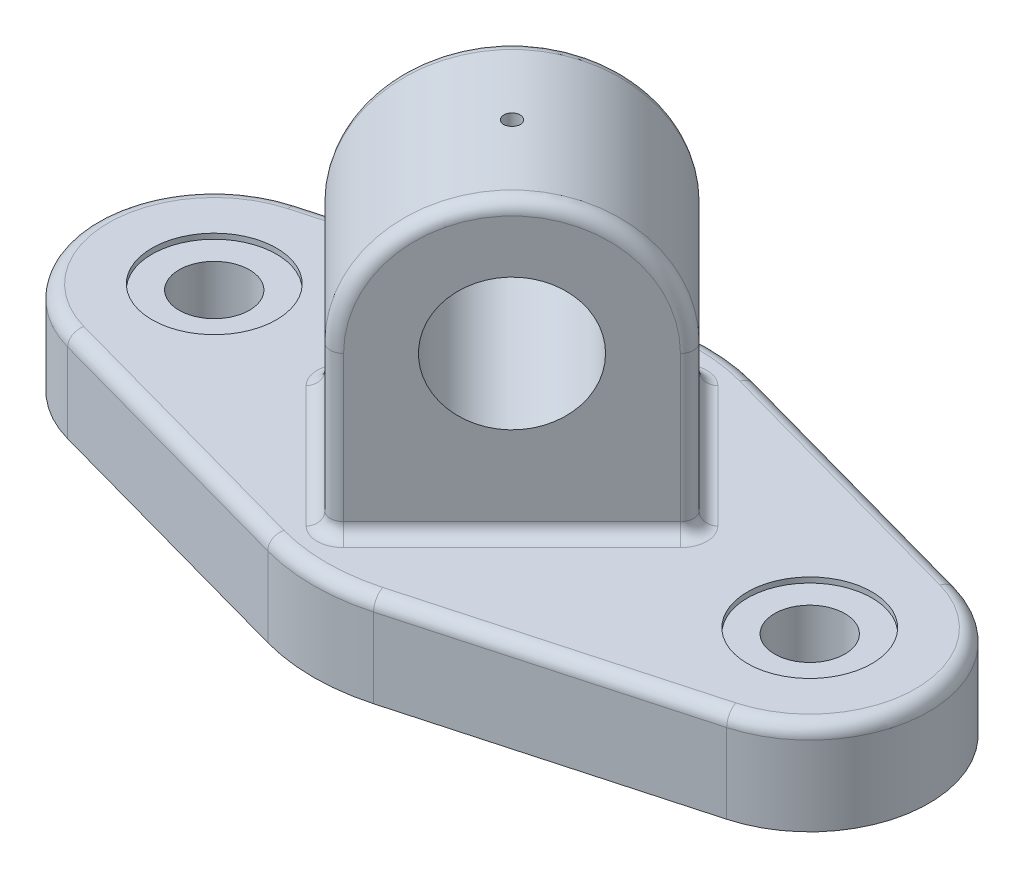
SolidWorks part; units mm, degrees
ref_plane "Front" through (0, 0, 0) normal (0, 0, 1) x (1, 0, 0)
ref_plane "Top" through (0, 0, 0) normal (0, 1, 0) x (1, 0, 0)
ref_plane "Right" through (0, 0, 0) normal (1, 0, 0) x (0, 0, -1)
sketch "Sketch1" plane through (0, 0, 0) normal (0, 1, 0) x (1, 0, 0)
  line L0 (-63.246, 22.0322) -> (-10.16, 36.7204)
  line L1 (-63.246, -22.0322) -> (-10.16, -36.7204)
  line L2 (0, 27.7769) -> (0, -27.7769)
  line L3 (63.246, -22.0322) -> (10.16, -36.7204)
  line L4 (63.246, 22.0322) -> (10.16, 36.7204)
  arc A0 (-10.16, -36.7204) -> (10.16, -36.7204) centre (0, 0) ccw
  arc A1 (-63.246, 22.0322) -> (-63.246, -22.0322) centre (-57.15, 0) ccw
  arc A2 (10.16, 36.7204) -> (-10.16, 36.7204) centre (0, 0) ccw
  arc A3 (63.246, 22.0322) -> (63.246, -22.0322) centre (57.15, 0) cw
  dimension "D1" = 57.15
  dimension "D2" = 38.1
  dimension "D3" = 22.86
  dimension "D5" = 22.86
  dimension "D4" = 114.3
extrude "Boss-Extrude2" add sketch "Sketch1" along normal blind 17.78 contours L0 A2 L4 A3 L3 A0 L1 A1
sketch "Sketch2" plane through (0, 17.78, 0) normal (0, 1, 0) x (1, 0, 0)
  circle A1 centre (-57.15, 0) radius 6.7437
  dimension "D1" = 13.4874
extrude "Cut-Extrude1" cut sketch "Sketch2" against normal through all contours A1
sketch "Sketch3" plane through (0, 17.78, 0) normal (0, 1, 0) x (1, 0, 0)
  circle A0 centre (-57.15, 0) radius 11.938
  dimension "D1" = 23.876
extrude "Cut-Extrude2" cut sketch "Sketch3" against normal blind 1.016
mirror "Mirror1" about plane through (0, 0, 0) normal (1, 0, 0) of "Cut-Extrude1", "Cut-Extrude2"
ref_axis "Axis1" through (0, 81.6205, 0) along (0, -1, 0)
ref_plane "Plane1" through (0, 0, 0) normal (0.7071, 0, 0.7071) x (0, -1, 0)
sketch "Sketch8" plane through (0, 0, 0) normal (0.7071, 0, 0.7071) x (0, -1, 0)
  line L1 (-17.78, 0) -> (-31.9445, 0)
  line L4 (-17.78, 29.1425) -> (-17.78, -18.781)
  line L5 (-17.78, 29.1425) -> (-17.78, -18.781)
  line L7 (-48.26, -25.4) -> (-17.78, -25.4)
  line L8 (-17.78, -25.4) -> (-17.78, 25.4)
  line L9 (-17.78, 25.4) -> (-48.26, 25.4)
  arc A1 (-48.26, 25.4) -> (-48.26, -25.4) centre (-48.26, 0) ccw
  dimension "D4" = 25.4
  dimension "D5" = 25.4
  dimension "D1" = 0
extrude "Boss-Extrude3" add sketch "Sketch8" along normal blind 19.05 and the other way blind 19.05 contours A1 L7 L8 L9
sketch "Sketch9" plane through (13.4704, 0, 13.4704) normal (0.7071, 0, 0.7071) x (0.7071, 0, -0.7071)
  line L2 (-25.4, 17.78) -> (25.4, 17.78)
  line L3 (-25.4, 17.78) -> (25.4, 17.78)
  circle A0 centre (0, 48.26) radius 12.7
  dimension "D1" = 0
  dimension "D2" = 30.48
extrude "Cut-Extrude5" cut sketch "Sketch9" against normal through all contours A0
ref_plane "Plane5" through (0, 73.66, 0) normal (0, 1, 0) x (1, 0, 0)
hole_wizard "1/8 (0.125) Diameter Hole14" positions "Sketch88" profile "Sketch89" hole size "1/8" standard "ANSI Inch" end condition up to next
sketch "Sketch88" plane through (0, 73.66, 0) normal (0, 1, 0) x (1, 0, 0)
  point P0 (0, 0)
sketch "Sketch89" plane through (0, 73.66, 0) normal (1, 0, 0) x (0, 0, 1)
  line L0 (0, 0) -> (0, 12.7)
  line L1 (0, 12.7) -> (1.5875, 12.7)
  line L2 (1.5875, 12.7) -> (1.5875, 0)
  line L5 (1.5875, 0) -> (0, 0)
  line L11 (0, -6.35) -> (0, 107.95) construction
  dimension "Thru Hole Dia." = 3.175
  dimension "Thru Hole Depth" = 12.7
fillet "Fillet1" radius 2.54 18 edges at (17.9605, 17.78, -17.9605) (-13.4704, 17.78, -13.4704) (13.4704, 17.78, 13.4704) (4.4901, 33.02, -31.4309) (-31.4309, 33.02, 4.4901) (31.4309, 33.02, -4.4901) (-4.4901, 33.02, 31.4309) (-80.01, 17.78, 0) (-36.703, 17.78, -29.3763) (0, 17.78, -38.1) (36.703, 17.78, -29.3763) (80.01, 17.78, 0) (36.703, 17.78, 29.3763) (0, 17.78, 38.1) (-17.9605, 17.78, 17.9605) (-13.4704, 73.66, -13.4704) (13.4704, 73.66, 13.4704) (-36.703, 17.78, 29.3763)
